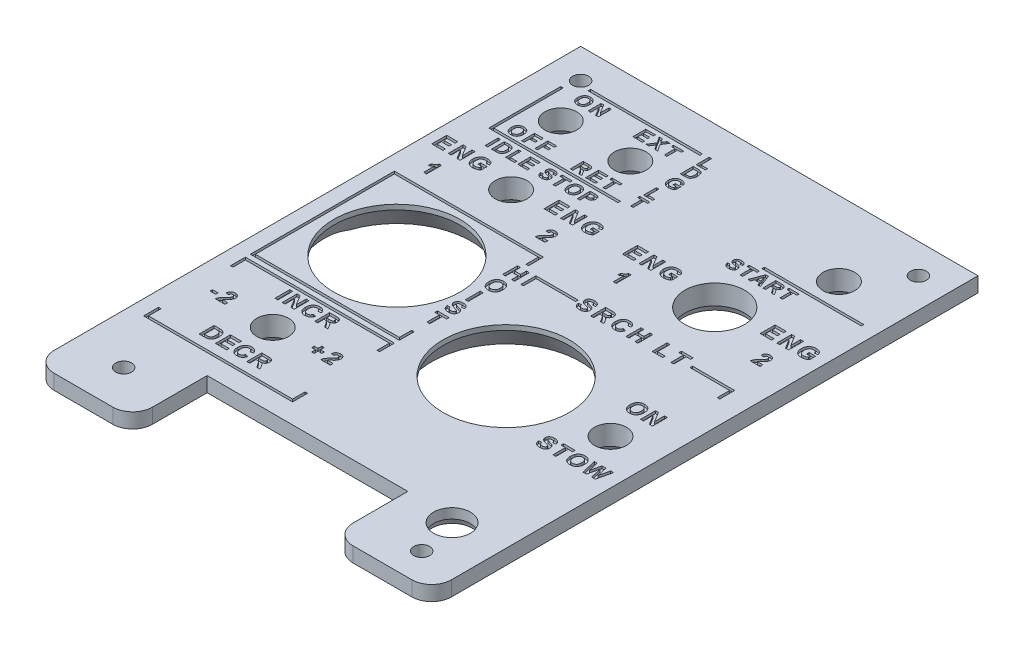
SolidWorks part; units mm, degrees
ref_plane "Спереди" through (0, 0, 0) normal (0, 0, 1) x (1, 0, 0)
ref_plane "Сверху" through (0, 0, 0) normal (0, 1, 0) x (1, 0, 0)
ref_plane "Справа" through (0, 0, 0) normal (1, 0, 0) x (0, 0, -1)
sketch "Sketch1" plane through (0, 0, 0) normal (0, 1, 0) x (1, 0, 0)
  line L1 (40, -55) -> (-40, -55)
  line L2 (40, -55) -> (40, 55)
  line L3 (40, 55) -> (-40, 55)
  line L4 (-40, -55) -> (-40, 55)
  line L5 (40, -55) -> (-40, 55) construction
  line L6 (40, 55) -> (-40, -55) construction
  point P0 (0, 0)
  dimension "D1" = 80
  dimension "D2" = 110
extrude "Boss-Extrude1" add sketch "Sketch1" along normal blind 3
sketch "Sketch2" plane through (0, 0, 55) normal (0, 0, 1) x (1, 0, 0)
  line L0 (0, 3) -> (0, 0) construction
  line L1 (-40, 3) -> (40, 3) construction
  line L2 (-40, 0) -> (40, 0) construction
  line L4 (20.2, 0) -> (-20.2, 0)
  line L5 (20.2, 0) -> (20.2, 3)
  line L6 (20.2, 3) -> (-20.2, 3)
  line L7 (-20.2, 0) -> (-20.2, 3)
  line L8 (20.2, 0) -> (-20.2, 3) construction
  line L9 (20.2, 3) -> (-20.2, 0) construction
  point P6 (0, 1.5)
  dimension "D1" = 40.4
extrude "Cut-Extrude1" cut sketch "Sketch2" against normal blind 15
fillet "Fillet1" radius 4 4 edges at (20.2, 1.5, 55) (40, 1.5, 55) (-20.2, 1.5, 55) (-40, 1.5, 55)
sketch "Sketch7" plane through (0, 0, 0) normal (0, -1, 0) x (1, 0, 0)
  line L0 (-40, -55) -> (-40, 51) construction
  line L1 (40, -55) -> (-40, -55) construction
  line L2 (36.8, 34.8) -> (-36.8, 34.8)
  line L3 (36.8, 34.8) -> (36.8, -51.8)
  line L4 (36.8, -51.8) -> (-36.8, -51.8)
  line L5 (-36.8, 34.8) -> (-36.8, -51.8)
  line L6 (36.8, 34.8) -> (-36.8, -51.8) construction
  line L7 (40, 51) -> (40, -55) construction
  line L8 (36.8, -51.8) -> (-36.8, 34.8) construction
  point P0 (0, -8.5)
  point P11 (0, 34.8)
  point P12 (0, -55)
  dimension "D1" = 3.2
  dimension "D2" = 3.2
  dimension "D3" = 3.2
  dimension "D4" = 89.8
extrude "Boss-Extrude2" add sketch "Sketch7" along normal blind 2
sketch "Sketch3" plane through (0, 3, 0) normal (0, 1, 0) x (1, 0, 0)
  line L0 (-40, 0) -> (40, 0) construction
  line L1 (-40, 55) -> (-40, -51) construction
  line L2 (40, -51) -> (40, 55) construction
  line L3 (-40, -10) -> (40, -10) construction
  line L4 (20.2, -40) -> (-20.2, -40) construction
  circle A0 centre (-22, 0) radius 12.7
  circle A1 centre (10, -10) radius 12.7
  point P10 (0, -10)
  point P13 (0, -40)
  point P16 (0, 0)
  dimension "D1" = 25.4
  dimension "D2" = 30
  dimension "D3" = 40
  dimension "D4" = 18
  dimension "D5" = 30
extrude "Cut-Extrude2" cut sketch "Sketch3" against normal through all
sketch "Sketch4" plane through (0, 3, 0) normal (0, 1, 0) x (1, 0, 0)
  line L0 (40, -51) -> (40, 55) construction
  line L1 (40, 55) -> (-40, 55) construction
  line L2 (19, 55) -> (19, -40) construction
  line L3 (40, -40) -> (-40, -40) construction
  line L4 (-40, 55) -> (-40, -51) construction
  line L5 (20.2, -40) -> (-20.2, -40) construction
  line L6 (40, 23) -> (-40, 23) construction
  line L7 (-22, 0) -> (-22, 55) construction
  line L8 (10, -10) -> (40, -10) construction
  line L9 (20.2, -41) -> (40, -41) construction
  line L10 (20.2, -40) -> (20.2, -51) construction
  line L11 (24.2, -55) -> (36, -55) construction
  line L12 (40, 40) -> (-40, 40) construction
  line L13 (-40, -25) -> (40, -25) construction
  line L15 (-22, 0) -> (-22, -54.3407) construction
  line L16 (-36, -55) -> (-24.2, -55) construction
  line L17 (-40, 49) -> (40, 49) construction
  line L18 (32, -41) -> (32, -55) construction
  line L19 (24.2, -55) -> (36, -55) construction
  circle A0 centre (19, 23) radius 6
  circle A1 centre (-22, 23) radius 3.2
  circle A2 centre (31, -10) radius 3.2
  circle A3 centre (30.1, -41) radius 3.7
  circle A4 centre (-29, 40) radius 3.2
  circle A5 centre (-15, 40) radius 3.2
  circle A6 centre (27, 40) radius 3.2
  circle A7 centre (-22, -25) radius 3.2
  arc A8 (-24.2, -55) -> (-20.2, -51) centre (-24.2, -51) ccw construction
  circle A9 centre (-30, -47) radius 1.6
  circle A10 centre (-34, 49) radius 1.6
  circle A11 centre (34, 49) radius 1.6
  circle A12 centre (32, -49) radius 1.6
  point P12 (0, -40)
  point P61 (0, 49)
  dimension "D1" = 12
  dimension "D7" = 7.4
  dimension "D8" = 14
  dimension "D14" = 6.4
  dimension "D17" = 3.2
  dimension "D20" = 3.2
  dimension "D25" = 3.2
  dimension "D27" = 13
  dimension "D2" = 21
  dimension "D3" = 32
  dimension "D6" = 9
  dimension "D12" = 14
  dimension "D13" = 7
  dimension "D15" = 30
  dimension "D16" = 15
  dimension "D18" = 10
  dimension "D19" = 8
  dimension "D21" = 68
  dimension "D22" = 34
  dimension "D23" = 6
  dimension "D24" = 8
  dimension "D26" = 6
extrude "Cut-Extrude3" cut sketch "Sketch4" against normal through all
chamfer "Chamfer2" distance 1.5 angle 20 4 edges at (36.8, -2, -8.5) (0, -2, -51.8) (-36.8, -2, -8.5) (0, -2, 34.8) first distance on face at (36.8, -1, -8.5) first distance on face at (0, -1, -51.8) first distance on face at (-36.8, -1, -8.5) first distance on face at (0, -1, 34.8)
chamfer "Chamfer3" distance 4 angle 30 2 edges at (-22, -2, 12.7) (10, -2, 22.7) first distance on face at (-22, -2, 12.7) first distance on face at (10, -2, 22.7)
sketch "Sketch8" plane through (0, 3, 0) normal (0, 1, 0) x (1, 0, 0)
  line L0 (-35, 46) -> (-35, 48.5) construction
  line L1 (-35, 48.5) -> (-9, 48.5) construction
  line L2 (-9, 48.5) -> (-9, 46) construction
  line L3 (-9, 46) -> (-9.5, 46) construction
  line L4 (-9.5, 46) -> (-9.5, 48) construction
  line L5 (-9.5, 48) -> (-34.5, 48) construction
  line L6 (-34.5, 48) -> (-34.5, 46) construction
  line L7 (-34.5, 46) -> (-35, 46) construction
  line L8 (-29, 40) -> (-15, 40) construction
  line L9 (31, -10) -> (10, -10) construction
  line L10 (10, -22.7) -> (10, 2.7) construction
  line L11 (-22, 48) -> (-22, 32) construction
  line L12 (-9, 34) -> (-9, 31.5) construction
  line L13 (-9, 31.5) -> (-35, 31.5)
  line L14 (-35, 31.5) -> (-35, 34)
  line L15 (-35, 34) -> (-34.5, 34) construction
  line L16 (-34.5, 34) -> (-34.5, 32)
  line L17 (-34.5, 32) -> (-9.5, 32)
  line L18 (-9.5, 32) -> (-9.5, 34) construction
  line L19 (-9.5, 34) -> (-9, 34) construction
  line L20 (-37, 11.5) -> (-37, 14.5)
  line L21 (-37, 14.5) -> (-7, 14.5)
  line L22 (-7, 14.5) -> (-7, 11.5)
  line L23 (-7, 11.5) -> (-7.5, 11.5)
  line L24 (-7.5, 11.5) -> (-7.5, 14)
  line L25 (-7.5, 14) -> (-36.5, 14)
  line L26 (-36.5, 14) -> (-36.5, 11.5)
  line L27 (-36.5, 11.5) -> (-37, 11.5) construction
  line L28 (-4.5, 7.5) -> (-4.5, 10.5)
  line L29 (-22, 14) -> (-22, -14) construction
  line L30 (-7, -11.5) -> (-7, -14.5)
  line L31 (-7, -14.5) -> (-37, -14.5)
  line L32 (-37, -14.5) -> (-37, -11.5)
  line L33 (-37, -11.5) -> (-36.5, -11.5) construction
  line L34 (-36.5, -11.5) -> (-36.5, -14)
  line L35 (-36.5, -14) -> (-7.5, -14)
  line L36 (-7.5, -14) -> (-7.5, -11.5)
  line L37 (-7.5, -11.5) -> (-7, -11.5)
  line L38 (-22, 12.7) -> (-22, -12.7) construction
  line L39 (-4.5, 10.5) -> (35.5, 10.5) construction
  line L40 (35.5, 10.5) -> (35.5, 7.5)
  line L41 (35.5, 7.5) -> (35, 7.5)
  line L42 (35, 7.5) -> (35, 10)
  line L43 (35, 10) -> (-4, 10) construction
  line L44 (-4, 10) -> (-4, 7.5)
  line L45 (-4, 7.5) -> (-4.5, 7.5)
  line L46 (15.5, 10) -> (15.5, -10) construction
  line L47 (-37, -18.5) -> (-37, -15.5)
  line L48 (-37, -15.5) -> (-7, -15.5)
  line L49 (-7, -15.5) -> (-7, -18.5)
  line L50 (-7, -18.5) -> (-7.5, -18.5)
  line L51 (-7.5, -18.5) -> (-7.5, -16)
  line L52 (-7.5, -16) -> (-36.5, -16)
  line L53 (-36.5, -16) -> (-36.5, -18.5)
  line L54 (-36.5, -18.5) -> (-37, -18.5)
  line L55 (-22, -16) -> (-22, -34) construction
  line L56 (-7, -33) -> (-7, -36)
  line L57 (-7, -36) -> (-37, -36)
  line L58 (-37, -36) -> (-37, -33)
  line L59 (-37, -33) -> (-36.5, -33)
  line L60 (-36.5, -33) -> (-36.5, -35.5)
  line L61 (-36.5, -35.5) -> (-7.5, -35.5)
  line L62 (-7.5, -35.5) -> (-7.5, -33)
  line L63 (-7.5, -33) -> (-7, -33)
  line L64 (-78.7082, -66.728) -> (-78.7082, -92.128) construction
  line L65 (-18.8, -25) -> (-25.2, -25) construction
  line L66 (-35, 46) -> (-35, 34)
  line L67 (-34.5, 46) -> (-34.5, 34)
  line L68 (-9, 48.5) -> (-9, 48)
  line L69 (-9, 48) -> (-9.5, 48)
  line L70 (-9.5, 32) -> (-9, 32)
  line L71 (-9, 32) -> (-9, 31.5)
  line L72 (-37, -11.5) -> (-37, 11.5)
  line L73 (-36.5, 11.5) -> (-36.5, -11.5)
  line L74 (-22, -25) -> (-22, -35.5) construction
  line L75 (20.2, -40) -> (-20.2, -40) construction
  line L76 (40, -51) -> (40, 55) construction
  line L77 (37, 34.5) -> (17, 34.5)
  line L78 (37, 34.5) -> (37, 35)
  line L79 (37, 35) -> (17, 35)
  line L80 (17, 34.5) -> (17, 35)
  line L81 (37, 34.5) -> (17, 35) construction
  line L82 (37, 35) -> (17, 34.5) construction
  line L83 (40, 55) -> (-40, 55) construction
  line L84 (-35, 46) -> (-34.5, 46)
  line L85 (-31.5, 48.5) -> (-31.5, 48)
  line L86 (-31.5, 48) -> (-9.5, 48)
  line L87 (-9, 48.5) -> (-31.5, 48.5)
  line L88 (-4.5, 10.5) -> (4, 10.5)
  line L89 (4, 10.5) -> (4, 10)
  line L90 (4, 10) -> (-4, 10)
  line L91 (27, 10.5) -> (27, 10)
  line L92 (27, 10) -> (35, 10)
  line L93 (35.5, 10.5) -> (27, 10.5)
  circle A1 centre (-22, 0) radius 12.7 construction
  circle A2 centre (10, -10) radius 12.7 construction
  circle A3 centre (-22, -25) radius 3.2 construction
  point P12 (-22, 40)
  point P15 (-22, 32)
  point P39 (-22, -14)
  point P51 (-22, 0)
  point P64 (-22, 0)
  point P66 (20.5, -10)
  point P95 (-22, -25)
  point P96 (-22, -25)
  point P102 (27, 34.75)
  dimension "D14" = 4
  dimension "D1" = 0.5
  dimension "D2" = 0.5
  dimension "D3" = 26
  dimension "D4" = 2
  dimension "D5" = 16
  dimension "D6" = 30
  dimension "D7" = 28
  dimension "D8" = 40
  dimension "D9" = 5
  dimension "D10" = 20
  dimension "D11" = 9
  dimension "D12" = 0.5
  dimension "D13" = 0.5
  dimension "D15" = 20
  dimension "D16" = 3
  dimension "D17" = 20
  dimension "D18" = 3
  dimension "D19" = 23
  dimension "D20" = 0.5
  dimension "D21" = 0.5
  dimension "D22" = 0.5
chamfer "Chamfer4" distance 1 angle 20 8 edges at (30.1, 0, 44.7) (31, -2, 13.2) (-22, -2, 28.2) (-22, -2, -19.8) (-29, -2, -36.8) (-15, -2, -36.8) (19, -2, -17) (27, -2, -36.8) first distance on face at (30.1, 3, 44.7) first distance on face at (31, -2, 13.2) first distance on face at (-22, -2, 28.2) first distance on face at (-22, -2, -19.8) first distance on face at (-29, -2, -36.8) first distance on face at (-15, -2, -36.8) first distance on face at (19, -2, -17) first distance on face at (27, -2, -36.8)
extrude "Cut-Extrude4" cut sketch "Sketch8" against normal blind 0.5
sketch "Sketch9" plane through (0, 3, 0) normal (0, 1, 0) x (1, 0, 0)
  line L0 (-8, 48) -> (-8, 32) construction
  line L1 (-40, 55) -> (-40, -51) construction
  text T0 "<b><r90>  L D G L T</r></b>" font "Arial" height 2.6
  dimension "D1" = 32
extrude "Cut-Extrude5" cut sketch "Sketch9" against normal blind 0.5
sketch "Sketch10" plane through (0, 3, 0) normal (0, 1, 0) x (1, 0, 0)
  line L0 (-34.5, 32.6) -> (-9.2723, 32.6) construction
  line L1 (-34.5, 32) -> (-34.5, 46) construction
  line L2 (-9.2723, 44.5) -> (-34.5, 44.5) construction
  line L3 (-34.5, 44.5) -> (-34.5, 32.6) construction
  line L4 (-9.2723, 44.5) -> (-9.2723, 32.6) construction
  line L5 (-31.5, 48) -> (-9, 48) construction
  line L6 (-9, 32) -> (-34.5, 32) construction
  text T0 "<b>  ON    EXT</b>" font "Arial" height 2.6
  text T1 "<b> OFF   RET</b>" font "Arial" height 2.6
  dimension "D1" = 0.6
  dimension "D2" = 3.5
extrude "Cut-Extrude6" cut sketch "Sketch10" against normal blind 0.5
sketch "Sketch11" plane through (0, 3, 0) normal (0, 1, 0) x (1, 0, 0)
  line L0 (40, 31.2) -> (0, 31.2) construction
  line L1 (40, -51) -> (40, 55) construction
  line L2 (40, 55) -> (-40, 55) construction
  line L3 (40, 23) -> (-40, 23) construction
  line L4 (-40, 55) -> (-40, -51) construction
  text T0 "<b>          START</b>" font "Arial" height 2.6
  text T1 "<b> ENG       ENG   ENG          ENG</b>\r\n   <b>1            2  </b>   <b>  1               2  </b>" font "Arial" height 3
  dimension "D1" = 40
  dimension "D2" = 23.8
  dimension "D3" = 32
extrude "Cut-Extrude7" cut sketch "Sketch11" against normal blind 0.5
sketch "Sketch12" plane through (0, 3, 0) normal (0, 1, 0) x (1, 0, 0)
  line L0 (40, 9) -> (-40, 9) construction
  line L1 (40, -51) -> (40, 55) construction
  line L2 (-40, 55) -> (-40, -51) construction
  line L3 (27, 10) -> (35, 10) construction
  line L4 (40, -4) -> (-40, -4) construction
  line L5 (40, -19) -> (-40, -19) construction
  line L6 (34.2, -10) -> (27.8, -10) construction
  circle A0 centre (31, -10) radius 3.2 construction
  text T0 "<b>                          SRCH LT</b>" font "Arial" height 3
  text T1 "<b>                                               ON</b>\r\n\r\n\r\n<b>                                                                                    </b>" font "Arial" height 3
  text T2 "<b>                                             STOW</b>" font "Arial" height 3
  dimension "D1" = 1
  dimension "D2" = 15
  dimension "D3" = 9
extrude "Cut-Extrude8" cut sketch "Sketch12" against normal blind 0.5
sketch "Sketch13" plane through (0, 3, 0) normal (0, 1, 0) x (1, 0, 0)
  line L0 (-8.4, 12) -> (-8.4, -12) construction
  line L1 (-40, -0.8) -> (40, -0.8) construction
  line L2 (-40, 55) -> (-40, -51) construction
  line L3 (40, -51) -> (40, 55) construction
  line L4 (40, 55) -> (-40, 55) construction
  text T0 "<b>    <r90>H O    S T</r></b>" font "Arial" height 3
  text T1 "<b>                            I</b>" font "Arial" height 3
  dimension "D1" = 31.6
  dimension "D2" = 55.8
extrude "Cut-Extrude9" cut sketch "Sketch13" against normal blind 0.5
sketch "Sketch14" plane through (0, 3, 0) normal (0, 1, 0) x (1, 0, 0)
  line L0 (-40, 28.1) -> (40, 28.1) construction
  line L1 (-40, 55) -> (-40, -51) construction
  line L2 (40, -51) -> (40, 55) construction
  line L3 (-35, 31.5) -> (-9, 31.5) construction
  text T0 "<b>      IDLE STOP</b>" font "Arial" height 2.6
  dimension "D1" = 3.4
extrude "Cut-Extrude10" cut sketch "Sketch14" against normal blind 0.5
sketch "Sketch15" plane through (0, 3, 0) normal (0, 1, 0) x (1, 0, 0)
  line L0 (-40, -19.7) -> (40, -19.7) construction
  line L1 (-40, 55) -> (-40, -51) construction
  line L2 (40, -51) -> (40, 55) construction
  line L3 (40, -33.56) -> (-40, -33.56) construction
  line L6 (-18.8, -25) -> (-25.2, -25) construction
  line L7 (-40, -25.7935) -> (40, -25.7935) construction
  circle A0 centre (-22, -25) radius 3.2 construction
  text T0 "<b>         INCR</b>" font "Arial" height 3
  text T1 "<b>        DECR</b>" font "Arial" height 3
  text T2 "<b>   -2         +2</b>" font "Arial" height 3
  dimension "D1" = 5.3
  dimension "D2" = 8.56
extrude "Cut-Extrude11" cut sketch "Sketch15" against normal blind 0.5
sketch "Sketch16" plane through (0, 3, 0) normal (0, 1, 0) x (1, 0, 0)
  circle A0 centre (-15, 40) radius 4.5
  circle A1 centre (-29, 40) radius 4.5
  circle A2 centre (31, -10) radius 4.5
  circle A3 centre (-22, -25) radius 4.5
  circle A4 centre (-22, 23) radius 4.5
  circle A5 centre (30.1, -41) radius 4.5
  circle A6 centre (27, 40) radius 4.5
  circle A7 centre (19, 23) radius 8.5
  dimension "D1" = 9
  dimension "D2" = 17
